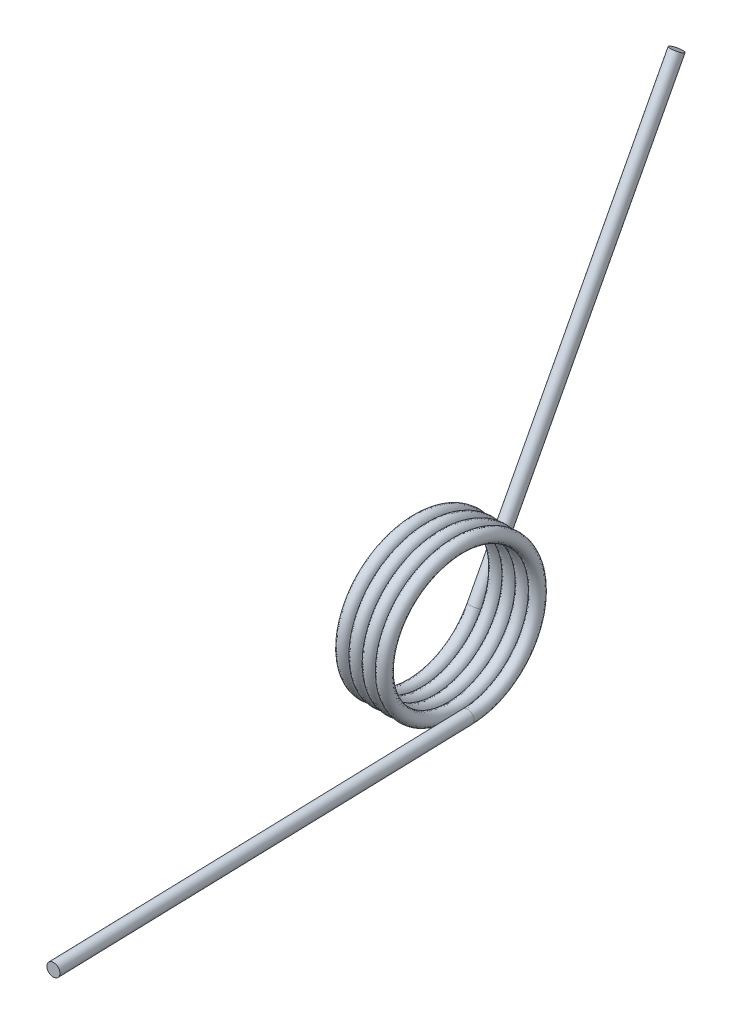
SolidWorks part; units mm, degrees
ref_plane "Front" through (0, 0, 0) normal (0, 0, 1) x (1, 0, 0)
ref_plane "Top" through (0, 0, 0) normal (0, 1, 0) x (1, 0, 0)
ref_plane "Right" through (0, 0, 0) normal (1, 0, 0) x (0, 0, -1)
sketch "Sketch1" plane through (0, 0, 0) normal (1, 0, 0) x (0, 0, -1)
  line L0 (0, -3.9751) -> (0, -4.7371) construction
  line L1 (4.1024, -2.3686) -> (16.8024, 19.6285) construction
  line L2 (0, -4.7371) -> (-25.4, -4.7371) construction
  line L3 (0, 0) -> (4.7371, 0) construction
  line L4 (0, 0) -> (4.1024, -2.3686) construction
  line L5 (-25.4, -4.7371) -> (-25.4, -3.9751) construction
  line L6 (-25.4, -3.9751) -> (0, -3.9751) construction
  line L7 (16.8024, 19.6285) -> (16.1425, 20.0095) construction
  line L8 (16.1425, 20.0095) -> (3.4425, -1.9876) construction
  circle A0 centre (0, 0) radius 4.7371 construction
  circle A1 centre (0, 0) radius 3.175 construction
  circle A2 centre (0, 0) radius 4.3561 construction
  point P7 (0, -4.3561)
  point P10 (0, 4.7371)
  dimension "OD" = 9.4742
  dimension "For Shaft Diameter" = 6.35
  dimension "Wire Diameter" = 0.762
  dimension "Leg Length" = 25.4
  dimension "Deflection Angle" = 120
sketch "Sketch2" plane through (0, 0, 0) normal (1, 0, 0) x (0, 0, -1)
  circle A0 centre (0, 0) radius 4.3561 construction
  circle A2 centre (0, 0) radius 4.3561
curve "Helix/Spiral1" pitch 0.7874 height 3.2808 turns 4.1667
ref_plane "Plane1" through (0, -4.3561, 0) normal (-0.0288, 0, -0.9996) x (0.9993, -0.0232, -0.0287)
sketch "Sketch3" plane through (0, -4.3561, 0) normal (-0.0288, 0, -0.9996) x (0.9993, -0.0232, -0.0287)
  circle A0 centre (0, 0) radius 0.381
  dimension "D1" = 0.762
sweep "Sweep1" add profiles "Sketch3" path "Helix/Spiral1"
sketch "Sketch4" plane through (0, 0, 0) normal (0.0288, 0, 0.9996) x (-0.9993, 0.0232, 0.0287)
  circle A1 centre (-0.1012, 4.3549) radius 0.381
  circle A2 centre (-0.1012, 4.3549) radius 0.381
  dimension "D1" = 0
extrude "Extrude1" add sketch "Sketch4" along normal blind 25.4
sketch "Sketch5" plane through (-0.0027, 0.0817, -0.0472) normal (-0.0288, 0.8657, -0.4998) x (0.9996, 0.0249, -0.0143)
  circle A1 centre (-3.2796, 4.356) radius 0.381
  circle A2 centre (-3.2796, 4.356) radius 0.381
  dimension "D1" = 0
extrude "Extrude2" add sketch "Sketch5" along normal blind 25.4
sketch "Sketch6" plane through (0, 0, 0) normal (1, 0, 0) x (0, 0, -1)
  circle A2 centre (0, 0) radius 3.9751 construction
equation "\"D4@Helix/Spiral1\" = \"Wire Diameter@Sketch1\" + .001"
equation "\"D1@Sketch3\"=\"Wire Diameter@Sketch1\""
equation "\"D1@Extrude2\"=\"Leg Length@Sketch1\""
equation "\"Leg Length@Extrude1\"=\"Leg Length@Sketch1\""
